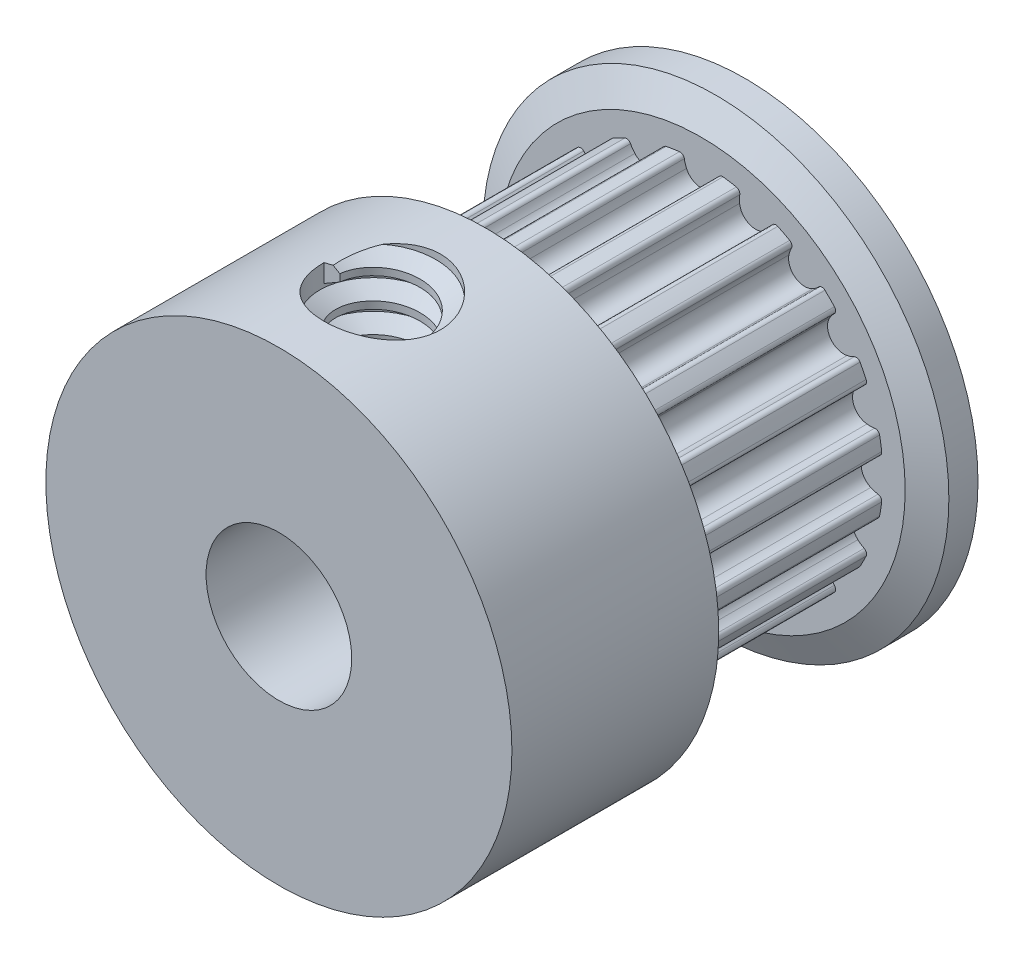
SolidWorks part; units mm, degrees
ref_plane "Front Plane" through (0, 0, 0) normal (0, 0, 1) x (1, 0, 0)
ref_plane "Top Plane" through (0, 0, 0) normal (0, 1, 0) x (1, 0, 0)
ref_plane "Right Plane" through (0, 0, 0) normal (1, 0, 0) x (0, 0, -1)
sketch "Sketch1" plane through (0, 0, 0) normal (0, 0, 1) x (1, 0, 0)
  circle A0 centre (0, 0) radius 6.366
  dimension "D1" = 12.732
extrude "Base" add sketch "Sketch1" along normal blind 7.4
sketch "Sketch2" plane through (0, 0, 7.4) normal (0, 0, 1) x (1, 0, 0)
  line L0 (0, 0) -> (0, 6.239) construction
  line L1 (0, 0) -> (-1.928, 5.9336) construction
  line L2 (-0.976, 6.1622) -> (0, 0) construction
  line L3 (-0.976, 6.1622) -> (-0.9959, 6.2876)
  line L4 (0.976, 6.1622) -> (0.9959, 6.2876)
  arc A1 (-0.5814, 6.0687) -> (-0.5066, 5.8173) centre (0.4062, 6.2258) ccw
  arc A2 (-0.5066, 5.8173) -> (0.5066, 5.8173) centre (0, 6.044) ccw
  arc A3 (-0.5814, 6.0687) -> (-0.7475, 6.1941) centre (-0.7295, 6.0451) ccw
  arc A4 (0.5814, 6.0687) -> (0.5066, 5.8173) centre (-0.4062, 6.2258) cw
  arc A5 (0.5814, 6.0687) -> (0.7475, 6.1941) centre (0.7295, 6.0451) cw
  arc A6 (0.7475, 6.1941) -> (0.976, 6.1622) centre (0, 0) cw
  circle A7 centre (0, 0) radius 6.366 construction
  arc A8 (0.9959, 6.2876) -> (-0.9959, 6.2876) centre (0, 0) ccw
  arc A11 (-0.7475, 6.1941) -> (-0.976, 6.1622) centre (0, 0) ccw
  dimension "D1" = 6.239
  dimension "D3" = 2
  dimension "D4" = 1.11
  dimension "D7" = 0.3
  dimension "D2" = 18
  dimension "D5" = 0.195
  dimension "D6" = 9
  dimension "D8" = 0.4062
extrude "ToothCut" cut sketch "Sketch2" against normal through all
pattern_circular "TeethCuts" count 20 over 360 about axis through (0, 0, 0) along (0, 0, 1) of "ToothCut"
sketch "Sketch3" plane through (0, 0, 0) normal (0, 1, 0) x (1, 0, 0)
  line L0 (0, 0) -> (0, 1.5)
  line L1 (0, 1.5) -> (-8, 1.5)
  line L2 (-8, 1.5) -> (-8, 0.5)
  line L3 (-7, 0) -> (0, 0)
  line L4 (0, -7.4) -> (-8, -7.4)
  line L5 (-0.5066, -7.4) -> (0.5066, -7.4) construction
  line L6 (-8, -7.4) -> (-8, -14.5)
  line L7 (-8, -14.5) -> (0, -14.5)
  line L8 (0, -14.5) -> (0, -7.4)
  line L9 (-8, 0.5) -> (-7, 0)
  point P5 (-8, 0)
  dimension "D1" = 16
  dimension "D2" = 1.5
  dimension "D3" = 0.5
  dimension "D4" = 1
  dimension "D5" = 8
revolve "Body" add sketch "Sketch3" angle 360 about L8
sketch "Sketch4" plane through (0, 0, 0) normal (0, 0, 1) x (1, 0, 0)
  circle A0 centre (0, 0) radius 2.5
  dimension "D1" = 5
extrude "ShaftHole" cut sketch "Sketch4" along normal through all both and the other way through all
sketch "Sketch5" plane through (0, 0, 0) normal (0, 1, 0) x (1, 0, 0)
  line L0 (-8, -7.4) -> (-8, -14.5) construction
  line L3 (-8, -14.5) -> (8, -14.5) construction
  circle A0 centre (0, -10.95) radius 2
  dimension "D1" = 4
  dimension "D2" = 8
  dimension "D3" = 3.55
extrude "FixingHole" cut sketch "Sketch5" along normal through all
sketch "Croquis1" plane through (0, 0, 0) normal (0, 1, 0) x (1, 0, 0)
  line L5 (-3.6752, -13.5748) -> (3.6752, -13.5748)
  line L6 (-3.6752, -13.5748) -> (-3.6752, -8.3252)
  line L7 (-3.6752, -8.3252) -> (3.6752, -8.3252)
  line L8 (3.6752, -13.5748) -> (3.6752, -8.3252)
  line L9 (-3.6752, -13.5748) -> (3.6752, -8.3252) construction
  line L10 (-3.6752, -8.3252) -> (3.6752, -13.5748) construction
  circle A0 centre (0, -10.95) radius 2
extrude "Saliente-Extruir1" add sketch "Croquis1" along normal blind 8
sketch "Croquis15" plane through (0, 0, 14.5) normal (0, 0, 1) x (1, 0, 0)
  circle A0 centre (0, 0) radius 1.65
  circle A1 centre (0, 0) radius 2.5
extrude "Saliente-Extruir2" add sketch "Croquis15" against normal blind 16
sketch "Croquis16" plane through (0, 0, 14.5) normal (0, 0, 1) x (1, 0, 0)
  circle A0 centre (0, 0) radius 1.65
sketch "Croquis17" plane through (0, 8, 0) normal (0, 1, 0) x (1, 0, 0)
  circle A0 centre (0, -10.95) radius 2
extrude "Cortar-Extruir2" cut sketch "Croquis17" against normal blind 8
thread "Rosca2" pitch 1 method extrude profile "Perfil de rosca2" start angle 0, offset 0, length 6, pitch 1, diameter 4
ref_plane "Plano2" through (-2, 8, 10.95) normal (0, 0, 1) x (-1, 0, 0)
sketch "Perfil de rosca2" plane through (-2, 8, 10.95) normal (0, 0, 1) x (-1, 0, 0)
  line L0 (0, 0) -> (0, 1) construction
  line L11 (0, 0) -> (0, 0.875)
  line L12 (0, 0.875) -> (-0.5413, 0.5625)
  line L13 (-0.5413, 0.5625) -> (-0.5413, 0.3125)
  line L15 (-0.5413, 0.3125) -> (0, 0)
  line L17 (-0.5413, 0.4375) -> (0, 0.4375) construction
  point P2 (0, 0)
  dimension "Pitch" = 1
  dimension "Profile_Angle" = 60
  dimension "Profile_Land" = 0.25
  dimension "Profile_Height" = 0.5413
sketch "Croquis20" plane through (0, 0, 14.5) normal (0, 0, 1) x (1, 0, 0)
  circle A0 centre (0, 0) radius 1.65
extrude "Cortar-Extruir3" cut sketch "Croquis20" against normal blind 8
sketch "Croquis21" plane through (0, 0, 14.5) normal (0, 0, 1) x (1, 0, 0)
  circle A0 centre (0, 0) radius 8
extrude "Cortar-Extruir4" cut sketch "Croquis21" against normal blind 8 flip side to cut
sketch "Sketch6" plane through (0, 0, 14.5) normal (0, 0, 1) x (1, 0, 0)
  circle A0 centre (0, 0) radius 2.5
  dimension "D1" = 5
extrude "Cut-Extrude1" cut sketch "Sketch6" against normal through all
